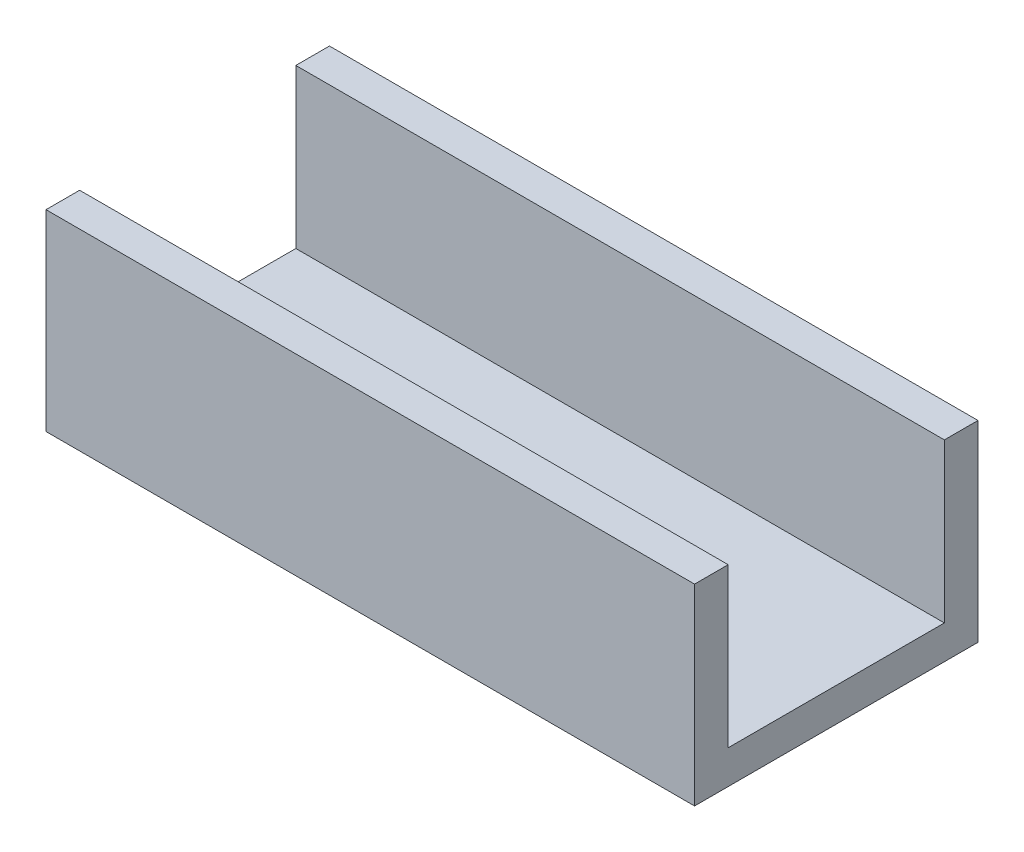
SolidWorks part; units mm, degrees
ref_plane "Спереди" through (0, 0, 0) normal (0, 0, 1) x (1, 0, 0)
ref_plane "Сверху" through (0, 0, 0) normal (0, 1, 0) x (1, 0, 0)
ref_plane "Справа" through (0, 0, 0) normal (1, 0, 0) x (0, 0, -1)
other "Configuration Table"
sketch "Эскиз1" plane through (0, 0, 0) normal (0, 1, 0) x (1, 0, 0)
  line L0 (0, 10.4) -> (27, 10.4)
  line L1 (0, 0) -> (27, 0)
  line L2 (0, 0) -> (0, 11.8)
  line L3 (0, 11.8) -> (27, 11.8)
  line L4 (27, 0) -> (27, 11.8)
  line L5 (27, 1.4) -> (0, 1.4)
  dimension "D1" = 27
  dimension "D2" = 11.8
  dimension "D3" = 1.4
  dimension "D4" = 1.4
extrude "Bottom" add sketch "Эскиз1" along normal blind 1.4 contours L5 L4 L0 L2 | L0 L4 L3 L2 | L4 L5 L2 L1 region at (13.5, 0, -11.1) region at (13.5, 0, -5.9) region at (13.5, 0, -0.7)
extrude "Бобышка-Вытянуть2" add sketch "Эскиз1<3>" along normal blind 8 contours L0 L4 L3 L2 | L4 L5 L2 L1 region at (13.5, 0, -11.1) region at (13.5, 0, -0.7)
sketch "Эскиз1<3>" plane through (0, 0, 0) normal (0, 1, 0) x (1, 0, 0) same geometry as "Эскиз1"
equation "\"D4@Эскиз1\"=\"D3@Эскиз1\""
